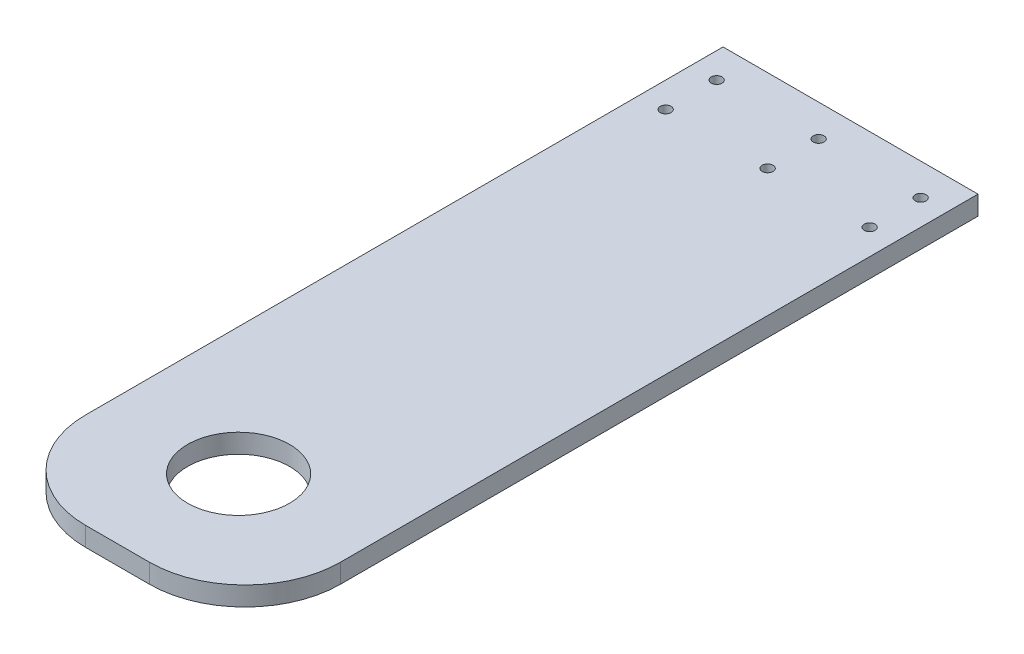
SolidWorks part; units mm, degrees
material "6061-T6 (SS)"
ref_plane "Front Plane" through (0, 0, 0) normal (0, 0, 1) x (1, 0, 0)
ref_plane "Top Plane" through (0, 0, 0) normal (0, 1, 0) x (1, 0, 0)
ref_plane "Right Plane" through (0, 0, 0) normal (1, 0, 0) x (0, 0, -1)
sketch "Sketch1" plane through (0, 0, 0) normal (0, 1, 0) x (1, 0, 0)
  line L1 (0, 0) -> (80, 0)
  line L2 (0, 0) -> (0, -230)
  line L3 (0, -230) -> (80, -230)
  line L4 (80, 0) -> (80, -230)
  dimension "D1" = 80
  dimension "D2" = 230
extrude "Boss-Extrude1" add sketch "Sketch1" along normal blind 6
sketch "Sketch5" plane through (0, 6, 0) normal (0, 1, 0) x (1, 0, 0)
  circle A1 centre (40, -192) radius 20
  circle A2 centre (40, -192) radius 48.5 construction
  point P1 (40, -192)
  point P5 (124.5769, -200.8167)
hole_wizard "Ø32.0 (32) Diameter Hole1" positions "Sketch5" profile "Sketch6" hole size "Ø32.0" standard "DIN" end condition through all
sketch "Sketch6" plane through (40, 6, 192) normal (1, 0, 0) x (0, 0, 1)
  line L0 (0, 0) -> (0, 6)
  line L1 (0, 6) -> (16, 6)
  line L2 (16, 6) -> (16, 0)
  line L5 (16, 0) -> (0, 0)
  line L11 (0, -6.35) -> (0, 107.95) construction
  dimension "Thru Hole Dia." = 32
  dimension "Thru Hole Depth" = 6
fillet "Fillet1" radius 30 2 edges at (0, 3, 230) (80, 3, 230)
sketch "Sketch9" plane through (0, 0, 0) normal (0, 1, 0) x (1, 0, 0)
  line L0 (40, 0) -> (40, -57.4233) construction
  line L1 (80, 0) -> (0, 0) construction
  point P0 (8, -10)
  point P6 (40, -10)
  point P7 (72, -10)
  point P8 (40, -26)
  point P9 (72, -26)
  point P10 (8, -26)
  dimension "D3" = 10
  dimension "D1" = 3
  dimension "D2" = 2
hole_wizard "CBORE for M3 Hex Socket Head Cap Screw1" positions "Sketch9" profile "Sketch8" counterbore size "M3" standard "DIN" end condition through all
sketch "Sketch8" plane through (8, 0, 10) normal (1, 0, 0) x (0, 0, -1)
  line L0 (0, 0) -> (0, 6)
  line L1 (0, 6) -> (1.7, 6)
  line L3 (1.7, 6) -> (1.7, 3.4)
  line L4 (1.7, 3.4) -> (3.25, 3.4)
  line L5 (3.25, 3.4) -> (3.25, 0)
  line L7 (3.25, 0) -> (0, 0)
  line L11 (0, -6.35) -> (0, 107.95) construction
  dimension "Thru Hole Dia." = 3.4
  dimension "Thru Hole Depth" = 6
  dimension "C'Bore Dia." = 6.5
  dimension "C'Bore Depth" = 3.4
